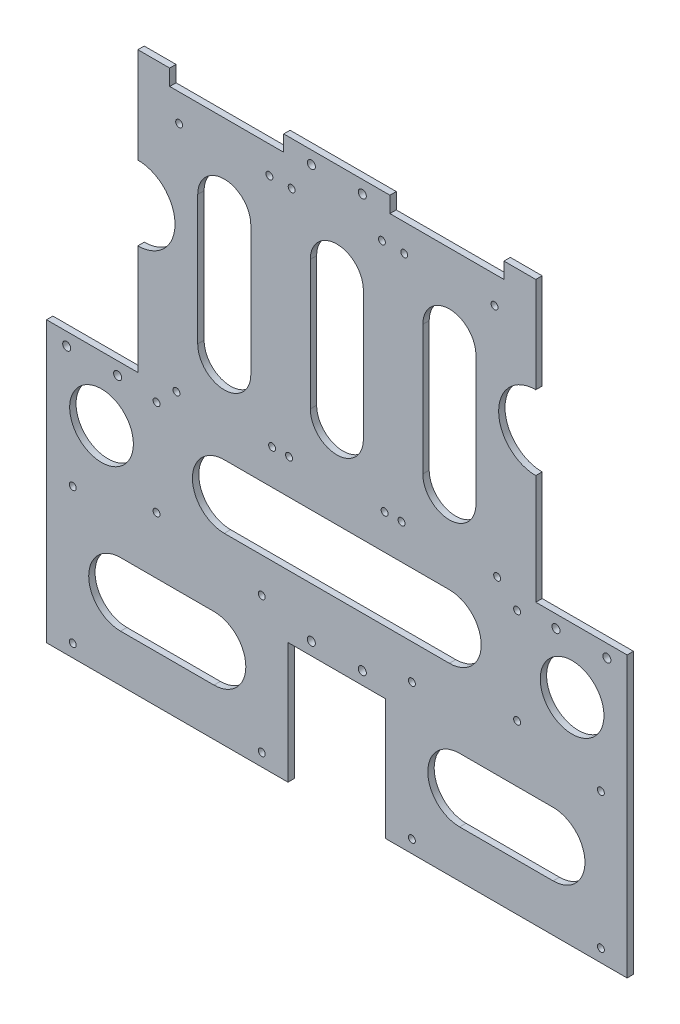
SolidWorks part; units mm, degrees
material "Oak"
ref_plane "Front Plane" through (0, 0, 0) normal (0, 0, 1) x (1, 0, 0)
ref_plane "Top Plane" through (0, 0, 0) normal (0, 1, 0) x (1, 0, 0)
ref_plane "Right Plane" through (0, 0, 0) normal (1, 0, 0) x (0, 0, -1)
sketch "Sketch1" plane through (0, 0, 0) normal (0, 0, 1) x (1, 0, 0)
  line L1 (0, 0) -> (273.4, 0)
  line L2 (0, 0) -> (0, -263.4)
  line L3 (0, -263.4) -> (273.4, -263.4)
  line L4 (273.4, 0) -> (273.4, -263.4)
  dimension "D1" = 273.4
  dimension "D2" = 263.4
extrude "Boss-Extrude1" add sketch "Sketch1" along normal blind 3
sketch "Sketch2" plane through (0, 0, 3) normal (0, 0, 1) x (1, 0, 0)
  line L1 (0, 0) -> (43, 0)
  line L2 (0, 0) -> (0, -131.64)
  line L3 (0, -131.64) -> (43, -131.64)
  line L4 (43, 0) -> (43, -131.64)
  line L9 (273.4, 0) -> (230.4, 0)
  line L10 (273.4, 0) -> (273.4, -131.64)
  line L11 (273.4, -131.64) -> (230.4, -131.64)
  line L12 (230.4, 0) -> (230.4, -131.64)
  dimension "D1" = 43
  dimension "D2" = 131.64
  dimension "D5" = 43
  dimension "D6" = 131.64
extrude "Cut-Extrude1" cut sketch "Sketch2" against normal through all
sketch "Sketch3" plane through (0, 0, 0) normal (0, 0, -1) x (-1, 0, 0)
  line L0 (0, -263.4) -> (-273.4, -263.4) construction
  line L1 (-159.7, -206.4) -> (-113.7, -206.4)
  line L2 (-159.7, -206.4) -> (-159.7, -263.4)
  line L3 (-159.7, -263.4) -> (-113.7, -263.4)
  line L4 (-113.7, -206.4) -> (-113.7, -263.4)
  line L5 (-273.4, -263.4) -> (-273.4, -131.64) construction
  dimension "D1" = 46
  dimension "D2" = 57
  dimension "D3" = 113.7
extrude "Cut-Extrude2" cut sketch "Sketch3" against normal through all
hole_wizard "#4 Clearance Hole1" positions "Sketch5" profile "Sketch6" hole size "#4" standard "ANSI Inch" end condition up to next
sketch "Sketch5" plane through (0, 0, 0) normal (0, 0, -1) x (-1, 0, 0)
  line L0 (-273.4, -263.4) -> (-273.4, -131.64) construction
  line L4 (-159.7, -263.4) -> (-273.4, -263.4) construction
  line L5 (-113.7, -263.4) -> (-113.7, -206.4) construction
  line L8 (-221.6, -139.4) -> (-51.8, -139.4) construction
  line L9 (-221.6, -139.4) -> (-221.6, -184.4) construction
  line L10 (-221.6, -184.4) -> (-51.8, -184.4) construction
  line L11 (-51.8, -139.4) -> (-51.8, -184.4) construction
  line L14 (-230.4, 0) -> (-230.4, -131.64) construction
  line L16 (-210.95, -20.4071) -> (-168.45, -20.4071) construction
  line L18 (-212.2, -130.4) -> (-167.2, -130.4) construction
  line L31 (-157.95, -20.4071) -> (-115.45, -20.4071) construction
  line L32 (-159.2, -130.4) -> (-114.2, -130.4) construction
  line L33 (-104.95, -20.4071) -> (-62.45, -20.4071) construction
  line L34 (-106.2, -130.4) -> (-61.2, -130.4) construction
  line L35 (-136.7, 0) -> (-136.7, -206.4) construction
  line L36 (-230.4, 0) -> (-43, 0) construction
  line L37 (-113.7, -206.4) -> (-159.7, -206.4) construction
  point P0 (-261.05, -257.4)
  point P2 (-261.05, -193.4)
  point P4 (-172.05, -193.4)
  point P6 (-172.05, -257.4)
  point P8 (-101.35, -257.4)
  point P10 (-101.35, -193.4)
  point P12 (-12.35, -193.4)
  point P14 (-12.35, -257.4)
  point P16 (-221.6, -139.4)
  point P18 (-221.6, -184.4)
  point P20 (-51.8, -139.4)
  point P22 (-51.8, -184.4)
  point P32 (-168.45, -20.4071)
  point P34 (-210.95, -20.4071)
  point P44 (-167.2, -130.4)
  point P46 (-212.2, -130.4)
  point P276 (-115.45, -20.4071)
  point P277 (-157.95, -20.4071)
  point P278 (-114.2, -130.4)
  point P279 (-159.2, -130.4)
  point P284 (-62.45, -20.4071)
  point P285 (-104.95, -20.4071)
  point P286 (-61.2, -130.4)
  point P287 (-106.2, -130.4)
  point P301 (-160.7661, -20.4071)
  point P302 (-136.7, -20.4071)
  dimension "D1" = 89
  dimension "D2" = 12.35
  dimension "D3" = 64
  dimension "D4" = 6
  dimension "D5" = 89
  dimension "D6" = 64
  dimension "D7" = 12.35
  dimension "D8" = 45
  dimension "D9" = 169.8
  dimension "D10" = 8.8
  dimension "D11" = 110
  dimension "D12" = 9
  dimension "D13" = 42.5
  dimension "D14" = 45
  dimension "D15" = 1.25
  dimension "D17" = 9
  dimension "D16" = 3
sketch "Sketch6" plane through (261.05, -257.4, 0) normal (1, 0, 0) x (0, 1, 0)
  line L0 (0, 0) -> (0, 3)
  line L1 (0, 3) -> (1.6319, 3)
  line L2 (1.6319, 3) -> (1.632, 0)
  line L5 (1.632, 0) -> (0, 0)
  line L11 (0, -6.35) -> (0, 107.95) construction
  dimension "Thru Hole Dia." = 3.2639
  dimension "Thru Hole Depth" = 3
sketch "Sketch4" plane through (0, 0, 3) normal (0, 0, 1) x (1, 0, 0)
  line L0 (230.4, 0) -> (43, 0) construction
  line L1 (58, 0) -> (111.7, 0)
  line L2 (58, 0) -> (58, -7.5)
  line L3 (58, -7.5) -> (111.7, -7.5)
  line L4 (111.7, 0) -> (111.7, -7.5)
  line L6 (43, -131.64) -> (43, 0) construction
  line L7 (136.7, 0) -> (136.7, -206.4) construction
  line L8 (113.7, -206.4) -> (159.7, -206.4) construction
  line L13 (0, -131.64) -> (0, -263.4) construction
  line L15 (43, -45) -> (43, -80)
  line L16 (230.4, -45) -> (230.4, -80)
  line L17 (215.4, -7.5) -> (161.7, -7.5)
  line L18 (161.7, 0) -> (161.7, -7.5)
  line L19 (215.4, 0) -> (161.7, 0)
  line L20 (215.4, 0) -> (215.4, -7.5)
  line L21 (51.8, -139.4) -> (51.8, -184.4) construction
  line L22 (51.8, -161.9) -> (0, -161.9) construction
  arc A0 (43, -45) -> (43, -80) centre (43, -62.5) cw
  circle A1 centre (25.9, -161.9) radius 15
  circle A2 centre (247.5, -161.9) radius 15
  arc A3 (230.4, -45) -> (230.4, -80) centre (230.4, -62.5) ccw
  point P21 (0, 0)
  point P22 (0, 0)
  point P36 (0, 0)
  dimension "D7" = 17.5
  dimension "D8" = 30
  dimension "D1" = 7.5
  dimension "D2" = 15
  dimension "D3" = 25
  dimension "D6" = 62.5
extrude "Cut-Extrude3" cut sketch "Sketch4" against normal up to next
hole_wizard "#6 Clearance Hole1" positions "Sketch7" profile "Sketch8" hole size "#6" standard "ANSI Inch" end condition up to next
sketch "Sketch7" plane through (0, 0, 3) normal (0, 0, 1) x (1, 0, 0)
  line L1 (111.7, -7.5) -> (111.7, 0) construction
  line L4 (113.7, -263.4) -> (113.7, -206.4) construction
  line L5 (0, -131.64) -> (43, -131.64) construction
  line L6 (113.7, -206.4) -> (159.7, -206.4) construction
  line L7 (230.4, -131.64) -> (273.4, -131.64) construction
  line L8 (161.7, 0) -> (111.7, 0) construction
  line L9 (0, -131.64) -> (0, -263.4) construction
  line L10 (273.4, -263.4) -> (273.4, -131.64) construction
  point P0 (124.7, -6)
  point P2 (148.7, -6)
  point P4 (9.5, -137.64)
  point P6 (33.5, -137.64)
  point P8 (124.7, -200.4)
  point P10 (148.7, -200.4)
  point P20 (263.9, -137.64)
  point P22 (239.9, -137.64)
  dimension "D1" = 24
  dimension "D2" = 24
  dimension "D3" = 24
  dimension "D4" = 24
  dimension "D5" = 13
  dimension "D6" = 11
  dimension "D7" = 6
  dimension "D8" = 6
  dimension "D9" = 6
  dimension "D10" = 6
  dimension "D11" = 9.5
  dimension "D12" = 9.5
sketch "Sketch8" plane through (124.7, -6, 3) normal (1, 0, 0) x (0, -1, 0)
  line L0 (0, 0) -> (0, 3)
  line L1 (0, 3) -> (1.8986, 3)
  line L2 (1.8986, 3) -> (1.8986, 0)
  line L5 (1.8986, 0) -> (0, 0)
  line L11 (0, -6.35) -> (0, 107.95) construction
  dimension "Thru Hole Dia." = 3.7973
  dimension "Thru Hole Depth" = 3
sketch "Sketch9" plane through (0, 0, 3) normal (0, 0, 1) x (1, 0, 0)
  line L0 (78.85, -226.216) -> (34.85, -226.216) construction
  line L1 (78.85, -241.216) -> (34.85, -241.216)
  line L2 (78.85, -211.216) -> (34.85, -211.216)
  line L3 (194.55, -226.216) -> (238.55, -226.216) construction
  line L6 (83.7, -161.9) -> (189.7, -161.9) construction
  line L7 (83.7, -146.9) -> (189.7, -146.9)
  line L8 (83.7, -176.9) -> (189.7, -176.9)
  line L9 (83.7, -44.9071) -> (83.7, -105.9) construction
  line L10 (96.2, -44.9071) -> (96.2, -105.9)
  line L11 (71.2, -44.9071) -> (71.2, -105.9)
  line L12 (136.7, -44.9071) -> (136.7, -105.9) construction
  line L13 (149.2, -44.9071) -> (149.2, -105.9)
  line L14 (124.2, -44.9071) -> (124.2, -105.9)
  line L15 (189.7, -44.9071) -> (189.7, -105.9) construction
  line L16 (202.2, -44.9071) -> (202.2, -105.9)
  line L17 (177.2, -44.9071) -> (177.2, -105.9)
  line L18 (136.7, 0) -> (136.7, -206.4) construction
  line L19 (161.7, 0) -> (111.7, 0) construction
  line L20 (113.7, -206.4) -> (159.7, -206.4) construction
  line L21 (51.8, -139.4) -> (51.8, -184.4) construction
  line L22 (51.8, -161.9) -> (157.8, -161.9) construction
  line L23 (12.35, -195.0319) -> (12.35, -257.4) construction
  line L24 (12.35, -257.4) -> (12.35, -226.216) construction
  line L25 (12.35, -226.216) -> (113.7, -226.216) construction
  line L26 (113.7, -263.4) -> (113.7, -206.4) construction
  line L27 (12.35, -193.4) -> (101.35, -193.4) construction
  line L28 (56.85, -193.4) -> (56.85, -263.4) construction
  line L29 (0, -263.4) -> (113.7, -263.4) construction
  line L30 (194.55, -241.216) -> (238.55, -241.216)
  line L31 (194.55, -211.216) -> (238.55, -211.216)
  arc A0 (78.85, -241.216) -> (78.85, -211.216) centre (78.85, -226.216) ccw
  arc A1 (34.85, -211.216) -> (34.85, -241.216) centre (34.85, -226.216) ccw
  arc A4 (83.7, -146.9) -> (83.7, -176.9) centre (83.7, -161.9) ccw
  arc A5 (189.7, -176.9) -> (189.7, -146.9) centre (189.7, -161.9) ccw
  arc A6 (96.2, -44.9071) -> (71.2, -44.9071) centre (83.7, -44.9071) ccw
  arc A7 (71.2, -105.9) -> (96.2, -105.9) centre (83.7, -105.9) ccw
  arc A8 (149.2, -44.9071) -> (124.2, -44.9071) centre (136.7, -44.9071) ccw
  arc A9 (124.2, -105.9) -> (149.2, -105.9) centre (136.7, -105.9) ccw
  arc A10 (202.2, -44.9071) -> (177.2, -44.9071) centre (189.7, -44.9071) ccw
  arc A11 (177.2, -105.9) -> (202.2, -105.9) centre (189.7, -105.9) ccw
  circle A12 centre (25.9, -161.9) radius 15 construction
  circle A13 centre (115.45, -20.4071) radius 1.6319 construction
  arc A14 (194.55, -241.216) -> (194.55, -211.216) centre (194.55, -226.216) cw
  circle A15 centre (159.2, -130.4) radius 1.6319 construction
  arc A16 (238.55, -211.216) -> (238.55, -241.216) centre (238.55, -226.216) cw
  circle A17 centre (12.35, -193.4) radius 1.632 construction
  circle A18 centre (101.35, -193.4) radius 1.6319 construction
  point P2 (56.85, -226.216)
  point P9 (216.55, -226.216)
  point P14 (136.7, -161.9)
  point P21 (83.7, -75.4036)
  point P28 (136.7, -75.4036)
  point P35 (189.7, -75.4036)
  point P72 (56.85, -226.216)
  point P79 (81.2559, -226.216)
  point P80 (233.7, -226.216)
  point P81 (218.0027, -226.216)
  dimension "D5" = 22.5
  dimension "D6" = 12.5
  dimension "D1" = 53
  dimension "D2" = 53
  dimension "D3" = 24.5
  dimension "D4" = 24.5
extrude "Cut-Extrude4" cut sketch "Sketch9" against normal up to next
